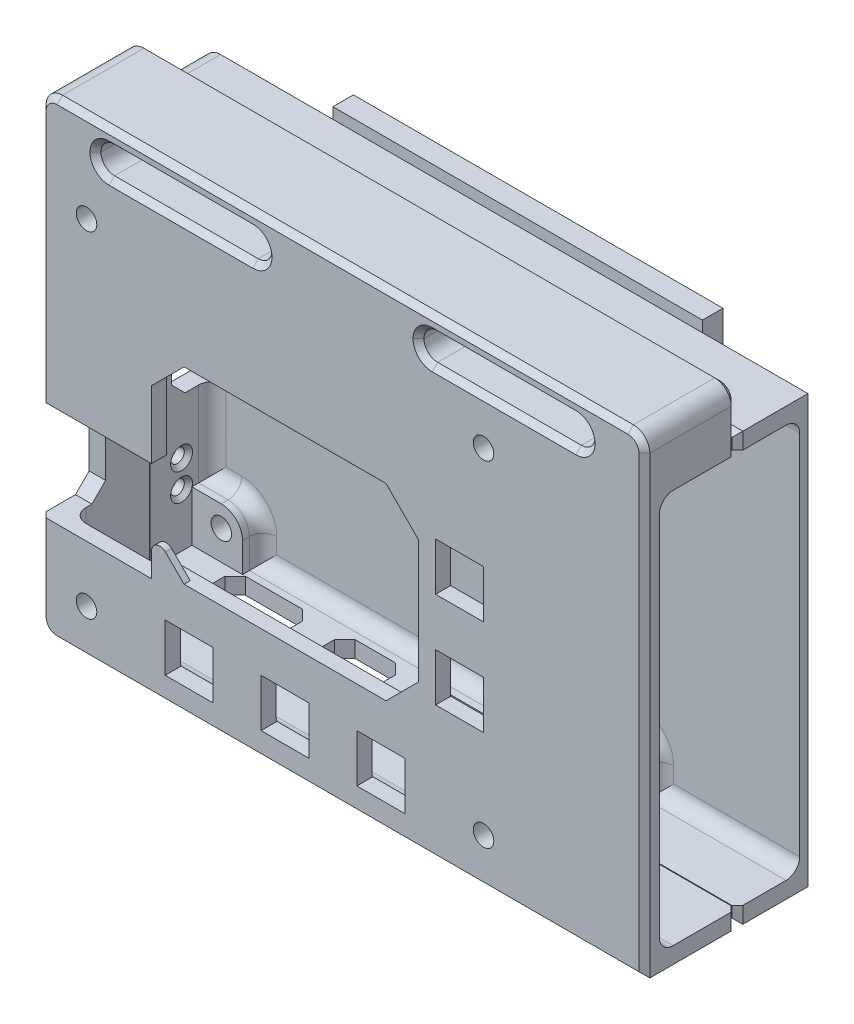
SolidWorks part; units mm, degrees
other "Bottom"
other "Top"
other "Charger-Plate" parameters "D1"=2, "D2"=2.4, "D3"=2.4, "D4"=4
ref_plane "Front Plane" through (0, 0, 0) normal (0, 0, 1) x (1, 0, 0)
ref_plane "Top Plane" through (0, 0, 0) normal (0, 1, 0) x (1, 0, 0)
ref_plane "Right Plane" through (0, 0, 0) normal (1, 0, 0) x (0, 0, -1)
ref_plane "Plane1" through (0, 0, 18.2875) normal (0, 0, 1) x (1, 0, 0)
sketch "Sketch1" plane through (0, 0, 16.2) normal (0, 0, 1) x (1, 0, 0)
  line L0 (13, 36.15) -> (17.75, 40.9)
  line L1 (17.75, 40.9) -> (47.25, 40.9)
  line L2 (47.25, 40.9) -> (52, 36.15)
  line L3 (52, 36.15) -> (52, 18.15)
  line L4 (52, 18.15) -> (47.25, 13.4)
  line L5 (47.25, 13.4) -> (17.75, 13.4)
  line L6 (17.75, 13.4) -> (13, 18.15)
  line L7 (13, 18.15) -> (13, 36.15)
  line L8 (13, 27.15) -> (52, 27.15) construction
  line L9 (32.5, 13.4) -> (32.5, 40.9) construction
  point P12 (32.5, 27.15)
sketch "Sketch2" plane through (0, 0, 18.2875) normal (0, 0, 1) x (1, 0, 0)
  line L0 (85, 56.8) -> (85, 59.2)
  line L1 (85, 59.2) -> (-3.2, 59.2)
  line L2 (-3.2, 59.2) -> (-3.2, -3.2)
  line L3 (-3.2, -3.2) -> (85, -3.2)
  line L4 (85, -3.2) -> (85, -0.8)
  line L5 (85, -0.8) -> (-0.8, -0.8)
  line L6 (-0.8, -0.8) -> (-0.8, 56.8)
  line L7 (-0.8, 56.8) -> (85, 56.8)
  line L8 (-0.8, 28) -> (-3.2, 28) construction
  line L9 (-0.8, 28) -> (0, 28) construction
  line L10 (0, 53) -> (0, 3) construction
  line L11 (42.1, 56.8) -> (42.1, 56) construction
  line L12 (82, 56) -> (3, 56) construction
  line L13 (42.1, -0.8) -> (42.1, 0) construction
  line L14 (3, 0) -> (82, 0) construction
  line L15 (85, 3) -> (85, 53) construction
  dimension "D1" = 0.8
  dimension "D2" = 2.4
extrude "Boss-Extrude1" add sketch "Sketch2" against normal offset from surface (13.1275 mm away) 2
sketch "Sketch3" plane through (0, 0, 18.2875) normal (0, 0, 1) x (1, 0, 0)
  line L1 (85, -3.2) -> (-3.2, -3.2)
  line L2 (85, -3.2) -> (85, 59.2)
  line L3 (85, 59.2) -> (-3.2, 59.2)
  line L4 (-3.2, -3.2) -> (-3.2, 59.2)
  line L5 (40.9, 59.2) -> (40.9, -3.2) construction
  line L6 (85, 28) -> (-3.2, 28) construction
  point P0 (40.9, 28)
extrude "Boss-Extrude2" add sketch "Sketch3" against normal blind 1.8 and the other way blind 0.4
extrude "Cut-Extrude1" cut sketch "Sketch1" along normal through all
sketch "Sketch4" plane through (0, 0, 16.4875) normal (0, 0, -1) x (-1, 0, 0)
  line L0 (-32.5, 40.9) -> (-32.5, 13.4) construction
  line L1 (-13, 40.9) -> (-52, 40.9)
  line L2 (-13, 40.9) -> (-13, 13.4)
  line L3 (-13, 13.4) -> (-52, 13.4)
  line L4 (-52, 40.9) -> (-52, 13.4)
  line L5 (-32.5, 13.4) -> (-32.5, 40.9) construction
  line L6 (-13, 27.15) -> (-52, 27.15) construction
  line L10 (-13, 13.4) -> (-52, 13.4) construction
  line L11 (-13, 40.9) -> (-52, 40.9) construction
  line L12 (-52, 36.15) -> (-52, 18.15) construction
  point P0 (-32.5, 27.15)
extrude "Cut-Extrude2" cut sketch "Sketch4" against normal offset from surface (1.3 mm away) 0.9 up to face at (40.9, 28, 18.6875)
sketch "Sketch15" plane through (0, 0, 16.4875) normal (0, 0, -1) x (-1, 0, 0)
  line L0 (-52, 10.1) -> (-52, 47.9) construction
  line L1 (-13, 49.9) -> (-52, 49.9)
  line L2 (-13, 49.9) -> (-13, 45.9)
  line L3 (-13, 45.9) -> (-52, 45.9)
  line L4 (-52, 49.9) -> (-52, 45.9)
  line L5 (-32.5, 45.9) -> (-32.5, 49.9) construction
  line L6 (-13, 47.9) -> (-52, 47.9) construction
  line L8 (-41, 12.1) -> (-52, 12.1)
  line L9 (-41, 12.1) -> (-41, 8.1)
  line L10 (-41, 8.1) -> (-52, 8.1)
  line L11 (-52, 12.1) -> (-52, 8.1)
  line L12 (-46.5, 8.1) -> (-46.5, 12.1) construction
  line L13 (-41, 10.1) -> (-52, 10.1) construction
  line L14 (-24, 12.1) -> (-13, 12.1)
  line L15 (-24, 12.1) -> (-24, 8.1)
  line L16 (-24, 8.1) -> (-13, 8.1)
  line L17 (-13, 12.1) -> (-13, 8.1)
  line L18 (-18.5, 8.1) -> (-18.5, 12.1) construction
  line L19 (-24, 10.1) -> (-13, 10.1) construction
  point P0 (-32.5, 47.9)
  point P5 (-18.5, 10.1)
  point P8 (-46.5, 10.1)
  dimension "D1" = 4
  dimension "D2" = 11
extrude "Cut-Extrude8" cut sketch "Sketch15" against normal blind 1
sketch "Sketch5" plane through (0, 0, 16.4875) normal (0, 0, -1) x (-1, 0, 0)
  line L0 (-52.8159, -0.8) -> (-64.6, -0.8)
  line L1 (-64.6, -0.8) -> (-64.6, 3.5)
  line L2 (-59.308, 5.692) -> (-52.8159, -0.8)
  line L3 (-85, -0.8) -> (0.8, -0.8) construction
  line L4 (-6.6, 3.5) -> (-6.6, -0.8)
  line L5 (-6.6, -0.8) -> (0.8, -0.8)
  line L7 (-3.5, 6.6) -> (0.8, 6.6)
  line L8 (0.8, 6.6) -> (0.8, -0.8)
  line L9 (-980.0493, 28) -> (49019.9507, 28) construction
  line L10 (0.8, 49.4) -> (0.8, 56.8)
  line L11 (-3.5, 49.4) -> (0.8, 49.4)
  line L12 (-6.6, 56.8) -> (0.8, 56.8)
  line L13 (-6.6, 52.5) -> (-6.6, 56.8)
  line L14 (-59.308, 50.308) -> (-52.8159, 56.8)
  line L15 (-64.6, 56.8) -> (-64.6, 52.5)
  line L16 (-52.8159, 56.8) -> (-64.6, 56.8)
  arc A0 (-64.6, 3.5) -> (-59.308, 5.692) centre (-61.5, 3.5) cw
  circle A1 centre (-61.5, 3.5) radius 1.5
  circle A2 centre (-61.5, 3.5) radius 1.5 construction
  arc A3 (-6.6, 3.5) -> (-3.5, 6.6) centre (-3.5, 3.5) cw
  circle A4 centre (-3.5, 3.5) radius 1.5
  circle A5 centre (-3.5, 3.5) radius 1.5 construction
  circle A6 centre (-3.5, 52.5) radius 1.5
  arc A7 (-6.6, 52.5) -> (-3.5, 49.4) centre (-3.5, 52.5) ccw
  circle A8 centre (-61.5, 52.5) radius 1.5
  arc A9 (-64.6, 52.5) -> (-59.308, 50.308) centre (-61.5, 52.5) ccw
  point P6 (-61.5, 6.6)
  point P7 (-61.5, 5)
  point P39 (-61.5, 51)
  point P40 (-61.5, 49.4)
  dimension "D1" = 3
  dimension "D2" = 1.6
  dimension "D3" = 45
extrude "Boss-Extrude3" add sketch "Sketch5" along normal up to surface (2.8875 mm away)
sketch "Sketch17" plane through (0, 0, 16.4875) normal (0, 0, -1) x (-1, 0, 0)
  circle A0 centre (-3.5, 3.5) radius 1.5 construction
  circle A1 centre (-3.5, 52.5) radius 1.5 construction
  circle A2 centre (-61.5, 52.5) radius 1.5 construction
  circle A3 centre (-61.5, 3.5) radius 1.5 construction
  circle A4 centre (-3.5, 3.5) radius 1.5
  circle A5 centre (-3.5, 52.5) radius 1.5
  circle A6 centre (-61.5, 52.5) radius 1.5
  circle A7 centre (-61.5, 3.5) radius 1.5
extrude "Cut-Extrude9" cut sketch "Sketch17" against normal through all
sketch "Sketch6" plane through (0, 0, 18.6875) normal (0, 0, 1) x (1, 0, 0)
  line L0 (54.5, 16.5) -> (61.5, 16.5)
  line L1 (61.5, 16.5) -> (61.5, 23.5)
  line L2 (61.5, 23.5) -> (54.5, 23.5)
  line L3 (54.5, 23.5) -> (54.5, 16.5)
  line L4 (55, 17) -> (61, 17)
  line L5 (55, 23) -> (55, 17)
  line L6 (61, 23) -> (55, 23)
  line L7 (61, 17) -> (61, 23)
  line L8 (55, 17) -> (61, 17) construction
  line L9 (55, 23) -> (55, 17) construction
  line L10 (61, 23) -> (55, 23) construction
  line L11 (61, 17) -> (61, 23) construction
  line L12 (55, 31) -> (61, 31)
  line L13 (55, 37) -> (55, 31)
  line L14 (61, 37) -> (55, 37)
  line L15 (61, 31) -> (61, 37)
  line L16 (55, 31) -> (61, 31) construction
  line L17 (55, 37) -> (55, 31) construction
  line L18 (61, 37) -> (55, 37) construction
  line L19 (61, 31) -> (61, 37) construction
  line L20 (15.5, 1) -> (21.5, 1)
  line L21 (15.5, 7) -> (15.5, 1)
  line L22 (21.5, 7) -> (15.5, 7)
  line L23 (21.5, 1) -> (21.5, 7)
  line L24 (15.5, 1) -> (21.5, 1) construction
  line L25 (15.5, 7) -> (15.5, 1) construction
  line L26 (21.5, 7) -> (15.5, 7) construction
  line L27 (21.5, 1) -> (21.5, 7) construction
  line L28 (43.5, 1) -> (49.5, 1)
  line L29 (43.5, 7) -> (43.5, 1)
  line L30 (49.5, 7) -> (43.5, 7)
  line L31 (49.5, 1) -> (49.5, 7)
  line L32 (43.5, 1) -> (49.5, 1) construction
  line L33 (43.5, 7) -> (43.5, 1) construction
  line L34 (49.5, 7) -> (43.5, 7) construction
  line L35 (49.5, 1) -> (49.5, 7) construction
  line L36 (29.5, 1) -> (35.5, 1)
  line L37 (29.5, 7) -> (29.5, 1)
  line L38 (35.5, 7) -> (29.5, 7)
  line L39 (35.5, 1) -> (35.5, 7)
  line L40 (29.5, 1) -> (35.5, 1) construction
  line L41 (29.5, 7) -> (29.5, 1) construction
  line L42 (35.5, 7) -> (29.5, 7) construction
  line L43 (35.5, 1) -> (35.5, 7) construction
  line L44 (54.5, 30.5) -> (61.5, 30.5)
  line L45 (61.5, 30.5) -> (61.5, 37.5)
  line L46 (61.5, 37.5) -> (54.5, 37.5)
  line L47 (54.5, 37.5) -> (54.5, 30.5)
  line L48 (15, 0.5) -> (22, 0.5)
  line L49 (22, 0.5) -> (22, 7.5)
  line L50 (22, 7.5) -> (15, 7.5)
  line L51 (15, 7.5) -> (15, 0.5)
  line L52 (43, 0.5) -> (50, 0.5)
  line L53 (50, 0.5) -> (50, 7.5)
  line L54 (50, 7.5) -> (43, 7.5)
  line L55 (43, 7.5) -> (43, 0.5)
  line L56 (29, 0.5) -> (36, 0.5)
  line L57 (36, 0.5) -> (36, 7.5)
  line L58 (36, 7.5) -> (29, 7.5)
  line L59 (29, 7.5) -> (29, 0.5)
  dimension "D1" = 0
  dimension "D2" = 0
  dimension "D3" = 0
  dimension "D4" = 0
  dimension "D5" = 0
  dimension "D6" = 0.5
extrude "Cut-Extrude3" cut sketch "Sketch6" against normal through all
sketch "Sketch7" plane through (0, 0, 18.6875) normal (0, 0, 1) x (1, 0, 0)
  line L0 (13, 18.15) -> (13, 36.15) construction
  line L1 (-3.2, 11.715) -> (13, 11.715)
  line L2 (-3.2, 11.715) -> (-3.2, 26.285)
  line L3 (-3.2, 26.285) -> (13, 26.285)
  line L4 (13, 11.715) -> (13, 26.285)
  line L5 (4.9, 26.285) -> (4.9, 11.715) construction
  line L6 (-3.2, 19) -> (13, 19) construction
  line L7 (-3.2, 59.2) -> (-3.2, -3.2) construction
  line L8 (-0.67, 19) -> (11.9, 19) construction
  line L9 (-0.67, 25.285) -> (11.9, 25.285) construction
  point P0 (4.9, 19)
  dimension "D1" = 1
extrude "Cut-Extrude4" cut sketch "Sketch7" against normal offset from surface (7.0875 mm away) 2 up to face at (3.5, 5, 13.6) offset beyond the face yes
sketch "Sketch8" plane through (0, 0, 5.16) normal (0, 0, -1) x (-1, 0, 0)
  line L8 (-85, 59.2) -> (-85, 56.8)
  line L9 (3.2, 59.2) -> (-85, 59.2)
  line L10 (3.2, -3.2) -> (3.2, 59.2)
  line L11 (-85, -3.2) -> (3.2, -3.2)
  line L12 (-85, -0.8) -> (-85, -3.2)
  line L13 (0.8, -0.8) -> (-85, -0.8)
  line L14 (0.8, 56.8) -> (0.8, -0.8)
  line L15 (-85, 56.8) -> (0.8, 56.8)
  line L16 (-85, 59.2) -> (-85, 56.8)
  line L17 (3.2, 59.2) -> (-85, 59.2)
  line L18 (3.2, -3.2) -> (3.2, 59.2)
  line L19 (-85, -3.2) -> (3.2, -3.2)
  line L20 (-85, -0.8) -> (-85, -3.2)
  line L21 (0.8, -0.8) -> (-85, -0.8)
  line L22 (0.8, 56.8) -> (0.8, -0.8)
  line L23 (-85, 56.8) -> (0.8, 56.8)
  dimension "D1" = 0
extrude "Boss-Extrude4" add sketch "Sketch8" along normal offset from surface (9.16 mm away) 3 separate body offset beyond the face yes
sketch "Sketch9" plane through (0, 0, -4) normal (0, 0, -1) x (-1, 0, 0)
  line L4 (-85, -3.2) -> (3.2, -3.2)
  line L5 (-85, 59.2) -> (-85, -3.2)
  line L6 (3.2, 59.2) -> (-85, 59.2)
  line L7 (3.2, -3.2) -> (3.2, 59.2)
  line L8 (-85, -3.2) -> (3.2, -3.2)
  line L9 (-85, 59.2) -> (-85, -3.2)
  line L10 (3.2, 59.2) -> (-85, 59.2)
  line L11 (3.2, -3.2) -> (3.2, 59.2)
  circle A0 centre (-3.5, 52.5) radius 1.5 construction
  circle A1 centre (-61.5, 52.5) radius 1.5 construction
  circle A2 centre (-61.5, 3.5) radius 1.5 construction
  circle A3 centre (-3.5, 3.5) radius 1.5 construction
  circle A4 centre (-3.5, 52.5) radius 1.5
  circle A5 centre (-61.5, 52.5) radius 1.5
  circle A6 centre (-61.5, 3.5) radius 1.5
  circle A7 centre (-3.5, 3.5) radius 1.5
  dimension "D1" = 0
extrude "Boss-Extrude5" add sketch "Sketch9" along normal blind 2
sketch "Sketch10" plane through (0, 0, -4) normal (0, 0, 1) x (1, 0, 0)
  line L3 (52.8159, -0.8) -> (64.6, -0.8)
  line L4 (64.6, -0.8) -> (64.6, 3.5)
  line L5 (59.308, 5.692) -> (52.8159, -0.8)
  line L6 (52.8159, -0.8) -> (64.6, -0.8)
  line L7 (64.6, -0.8) -> (64.6, 3.5)
  line L8 (59.308, 5.692) -> (52.8159, -0.8)
  line L9 (52.8159, 56.8) -> (59.308, 50.308)
  line L10 (-0.8, -0.8) -> (6.6, -0.8)
  line L11 (-0.8, 6.6) -> (-0.8, -0.8)
  line L12 (3.5, 6.6) -> (-0.8, 6.6)
  line L13 (6.6, -0.8) -> (6.6, 3.5)
  line L14 (-0.8, -0.8) -> (6.6, -0.8)
  line L15 (-0.8, 6.6) -> (-0.8, -0.8)
  line L16 (3.5, 6.6) -> (-0.8, 6.6)
  line L17 (6.6, -0.8) -> (6.6, 3.5)
  line L18 (64.6, 56.8) -> (52.8159, 56.8)
  line L19 (64.6, 52.5) -> (64.6, 56.8)
  line L20 (52.8159, 56.8) -> (59.308, 50.308)
  line L21 (64.6, 56.8) -> (52.8159, 56.8)
  line L22 (64.6, 52.5) -> (64.6, 56.8)
  line L24 (-0.8, 56.8) -> (-0.8, 49.4)
  line L25 (6.6, 56.8) -> (-0.8, 56.8)
  line L26 (6.6, 52.5) -> (6.6, 56.8)
  line L27 (-0.8, 49.4) -> (3.5, 49.4)
  line L28 (-0.8, 56.8) -> (-0.8, 49.4)
  line L29 (6.6, 56.8) -> (-0.8, 56.8)
  line L30 (6.6, 52.5) -> (6.6, 56.8)
  line L31 (-0.8, 49.4) -> (3.5, 49.4)
  circle A1 centre (3.5, 3.5) radius 1.5
  circle A2 centre (3.5, 3.5) radius 1.5
  circle A3 centre (61.5, 3.5) radius 1.5
  circle A4 centre (61.5, 3.5) radius 1.5
  arc A5 (64.6, 3.5) -> (59.308, 5.692) centre (61.5, 3.5) ccw
  arc A6 (64.6, 3.5) -> (59.308, 5.692) centre (61.5, 3.5) ccw
  circle A7 centre (61.5, 52.5) radius 1.5
  circle A8 centre (61.5, 52.5) radius 1.5
  circle A9 centre (3.5, 52.5) radius 1.5
  circle A10 centre (3.5, 52.5) radius 1.5
  arc A11 (6.6, 3.5) -> (3.5, 6.6) centre (3.5, 3.5) ccw
  arc A12 (6.6, 3.5) -> (3.5, 6.6) centre (3.5, 3.5) ccw
  arc A13 (59.308, 50.308) -> (64.6, 52.5) centre (61.5, 52.5) ccw
  arc A14 (59.308, 50.308) -> (64.6, 52.5) centre (61.5, 52.5) ccw
  arc A15 (3.5, 49.4) -> (6.6, 52.5) centre (3.5, 52.5) ccw
  arc A16 (3.5, 49.4) -> (6.6, 52.5) centre (3.5, 52.5) ccw
  dimension "D1" = 0
  dimension "D2" = 0
  dimension "D3" = 0
  dimension "D4" = 0
  dimension "D5" = 0
  dimension "D6" = 0
  dimension "D7" = 0
  dimension "D8" = 0
extrude "Boss-Extrude6" add sketch "Sketch10" along normal up to surface (3 mm away)
sketch "Sketch11" plane through (0, 0, -6) normal (0, 0, -1) x (-1, 0, 0)
  line L0 (3.2, 59.2) -> (3.2, -3.2) construction
  line L1 (-5.647, 37) -> (3.2, 37)
  line L2 (-5.647, 37) -> (-5.647, 19)
  line L3 (-5.647, 19) -> (3.2, 19)
  line L4 (3.2, 37) -> (3.2, 19)
  line L5 (-1.2235, 19) -> (-1.2235, 37) construction
  line L6 (-5.647, 28) -> (3.2, 28) construction
  line L7 (-85, 28) -> (3.2, 28) construction
  line L8 (-3.647, 22.4017) -> (-3.647, 30.9017) construction
  point P0 (-1.2235, 28)
  dimension "D1" = 18
  dimension "D2" = 2
extrude "Cut-Extrude5" cut sketch "Sketch11" against normal offset from surface (8 mm away) 2 offset beyond the face yes
sketch "Sketch12" plane through (0, -3.2, 0) normal (0, -1, 0) x (1, 0, 0)
  line L0 (50, 2.9) -> (50, 5.16)
  line L1 (85, 5.16) -> (-3.2, 5.16) construction
  line L2 (50, 5.16) -> (50.6996, 5.16)
  line L3 (58, 2.9) -> (58, 5.16)
  line L4 (58, 5.16) -> (57.3004, 5.16)
  line L5 (3, -1) -> (82, -1) construction
  line L6 (21.55, -1) -> (30.47, -1)
  line L7 (21.55, -1) -> (21.55, 5.16)
  line L8 (21.55, 5.16) -> (30.47, 5.16)
  line L9 (30.47, -1) -> (30.47, 5.16)
  line L10 (26.01, 5.16) -> (26.01, -1) construction
  line L11 (21.55, 2.08) -> (30.47, 2.08) construction
  line L12 (22.75, 2.4) -> (22.75, 1.0798) construction
  line L13 (9.95, 3.16) -> (12.45, 3.16) construction
  line L14 (35.05, -1) -> (43.97, -1)
  line L15 (35.05, -1) -> (35.05, 5.16)
  line L16 (35.05, 5.16) -> (43.97, 5.16)
  line L17 (43.97, -1) -> (43.97, 5.16)
  line L18 (39.51, 5.16) -> (39.51, -1) construction
  line L19 (35.05, 2.08) -> (43.97, 2.08) construction
  line L20 (5.53, -1) -> (16.87, -1)
  line L21 (5.53, -1) -> (5.53, 5.16)
  line L22 (5.53, 5.16) -> (16.87, 5.16)
  line L23 (16.87, -1) -> (16.87, 5.16)
  line L24 (11.2, 5.16) -> (11.2, -1) construction
  line L25 (5.53, 2.08) -> (16.87, 2.08) construction
  line L26 (15.67, -0.65) -> (15.67, 1.38) construction
  circle A0 centre (54, 2.9) radius 4 construction
  arc A1 (51, 2.9) -> (57, 2.9) centre (54, 2.9) ccw construction
  arc A2 (50, 2.9) -> (58, 2.9) centre (54, 2.9) ccw
  arc A3 (50.6996, 5.16) -> (57.3004, 5.16) centre (54, 2.9) cw
  point P5 (58, 2.9)
  point P18 (26.01, 2.08)
  point P26 (39.51, 2.08)
  point P30 (11.2, 2.08)
  point P36 (11.2, 3.16)
  dimension "D1" = 1
  dimension "D2" = 1.2
  dimension "D3" = 1.2
extrude "Cut-Extrude6" cut sketch "Sketch12" against normal up to surface (2.4 mm away) up to face at (41.6432, -0.8, -0.968)
chamfer "Chamfer1" distance 1.5 angle 45 6 edges at (5.53, -2, -1) (16.87, -2, -1) (30.47, -2, -1) (21.55, -2, -1) (35.05, -2, -1) (43.97, -2, -1)
fillet "Fillet1" radius 2 18 edges at (1.35, 49.4, -4) (6.6, 54.65, -4) (56.062, 53.554, -4) (64.6, 54.65, -4) (64.6, 1.35, -4) (56.062, 2.446, -4) (6.6, 1.35, -4) (1.35, 6.6, -4) (74.8, -0.8, -4) (-0.8, 12.8, -4) (29.708, -0.8, -4) (74.8, 56.8, -4) (29.708, 56.8, -4) (-0.8, 43.2, -4) (5.692, 50.308, -4) (62.6863, 49.636, -4) (62.6863, 6.364, -4) (5.692, 5.692, -4)
fillet "Fillet2" radius 2 18 edges at (64.6, 54.65, 16.4875) (56.062, 53.554, 16.4875) (6.6, 54.65, 16.4875) (1.35, 49.4, 16.4875) (1.35, 6.6, 16.4875) (6.6, 1.35, 16.4875) (56.062, 2.446, 16.4875) (64.6, 1.35, 16.4875) (29.708, 56.8, 16.4875) (74.8, 56.8, 16.4875) (62.6863, 49.636, 16.4875) (5.692, 50.308, 16.4875) (-0.8, 37.8425, 16.4875) (-0.8, 9.1575, 16.4875) (5.692, 5.692, 16.4875) (74.8, -0.8, 16.4875) (29.708, -0.8, 16.4875) (62.6863, 6.364, 16.4875)
sketch "Sketch14" plane through (0, 59.2, 0) normal (0, 1, 0) x (1, 0, 0)
  line L0 (-3.2, -5.16) -> (85, -5.16) construction
  line L1 (85, -5.11) -> (-3.2, -5.11)
  line L2 (85, -5.11) -> (85, -5.21)
  line L3 (85, -5.21) -> (-3.2, -5.21)
  line L4 (-3.2, -5.11) -> (-3.2, -5.21)
  line L5 (40.9, -5.21) -> (40.9, -5.11) construction
  line L6 (85, -5.16) -> (-3.2, -5.16) construction
  line L7 (-3.2, -5.16) -> (-3.2, -18.6875) construction
  point P0 (40.9, -5.16)
  dimension "D1" = 0.1
extrude "Cut-Extrude7" cut sketch "Sketch14" against normal through all
sketch "Sketch16" plane through (0, 0, 18.6875) normal (0, 0, 1) x (1, 0, 0)
  line L0 (4.8, 59.2) -> (-3.2, 59.2)
  line L1 (4.8, 59.2) -> (29.8, 59.2) construction
  line L2 (4.8, 59.2) -> (4.8, 63.2)
  line L3 (4.8, 63.2) -> (29.8, 63.2)
  line L4 (29.8, 59.2) -> (29.8, 63.2)
  line L5 (17.3, 63.2) -> (17.3, 59.2) construction
  line L6 (4.8, 61.2) -> (29.8, 61.2) construction
  line L7 (52, 59.2) -> (77, 59.2) construction
  line L8 (52, 59.2) -> (52, 63.2)
  line L9 (52, 63.2) -> (77, 63.2)
  line L10 (77, 59.2) -> (77, 63.2)
  line L11 (64.5, 63.2) -> (64.5, 59.2) construction
  line L12 (52, 61.2) -> (77, 61.2) construction
  line L13 (-3.2, 59.2) -> (-3.2, 65.6)
  line L14 (-3.2, 65.6) -> (85, 65.6)
  line L15 (85, 65.6) -> (85, 59.2)
  line L16 (85, 59.2) -> (77, 59.2)
  line L17 (17.3, 63.2) -> (17.3, 65.6) construction
  line L19 (52, 59.2) -> (29.8, 59.2)
  line L20 (-0.8, 28) -> (-3.2, 28) construction
  point P0 (17.3, 61.2)
  point P4 (64.5, 61.2)
  dimension "D1" = 25
  dimension "D2" = 4
  dimension "D3" = 8
  dimension "D4" = 72.2
extrude "Boss-Extrude7" add sketch "Sketch16" against normal up to surface (13.4775 mm away) up to face at (32.9336, 28, 5.21)
sketch "Sketch21" plane through (-3.2, 0, 0) normal (-1, 0, 0) x (0, 0, 1)
  line L0 (0, 53) -> (0, 3) construction
  circle A0 centre (0.5, 11) radius 1
  circle A1 centre (0.5, 7) radius 1
  point P4 (0, 0)
  dimension "D1" = 2
  dimension "D2" = 7
  dimension "D3" = 11
  dimension "D4" = 0.5
extrude "Cut-Extrude11" cut sketch "Sketch21" against normal blind 4
chamfer "Chamfer10" distance 0.6 angle 45 4 edges at (-0.8, 7, 1.5) (-3.2, 6, 0.5) (-0.8, 11, 1.5) (-3.2, 10, 0.5)
chamfer "Chamfer7" distance 0.8 angle 45 1 edges at (40.9, 65.6, 5.21)
fillet "Fillet3" radius 2 8 edges at (77, 59.2, 11.9487) (77, 63.2, 11.9487) (52, 63.2, 11.9487) (52, 59.2, 11.9487) (4.8, 59.2, 11.9487) (29.8, 59.2, 11.9487) (29.8, 63.2, 11.9487) (4.8, 63.2, 11.9487)
fillet "Fillet4" radius 2.4 3 edges at (-3.2, -3.2, 11.9487) (-3.2, 65.6, 12.3487) (85, 65.6, 12.3487)
fillet "Fillet5" radius 2.4 2 edges at (-3.2, -3.2, -0.445) (-3.2, 59.2, -0.445)
chamfer "Chamfer2" distance 0.8 angle 45 20 edges at (42.1, -3.2, 18.6875) (-2.4971, -2.4971, 18.6875) (-3.2, 5.4575, 18.6875) (85, 30, 18.6875) (-3.2, 44.7425, 18.6875) (84.2971, 64.8971, 18.6875) (-2.4971, 64.8971, 18.6875) (40.9, 65.6, 18.6875) (64.5, 63.2, 18.6875) (76.4142, 62.6142, 18.6875) (52.5858, 62.6142, 18.6875) (76.4142, 59.7858, 18.6875) (52.5858, 59.7858, 18.6875) (64.5, 59.2, 18.6875) (17.3, 63.2, 18.6875) (29.2142, 62.6142, 18.6875) (5.3858, 62.6142, 18.6875) (29.2142, 59.7858, 18.6875) (5.3858, 59.7858, 18.6875) (17.3, 59.2, 18.6875)
chamfer "Chamfer3" distance 0.8 angle 45 7 edges at (-3.2, 46.9, -6) (-3.2, 9.1, -6) (-2.4971, 58.4971, -6) (-2.4971, -2.4971, -6) (42.1, 59.2, -6) (42.1, -3.2, -6) (85, 28, -6)
fillet "Fillet6" radius 1.2 1 edges at (13, 18.15, 18.2375)
chamfer "Chamfer4-Screws-Countersink" [suppressed] distance 2 angle 45
chamfer "Chamfer5" distance 2 angle 45 2 edges at (-2, 19, 2) (-2, 37, 2)
chamfer "Chamfer6" distance 2 angle 45 2 edges at (-2, 26.285, 11.6) (-2, 11.715, 11.6)
sketch "Sketch18" plane through (0, 0, -6) normal (0, 0, -1) x (-1, 0, 0)
  line L0 (3.2, 59.2) -> (3.2, -3.2) construction
  line L1 (-121.8, 63) -> (3.2, 63) construction
  line L2 (-121.8, 63) -> (-121.8, -7) construction
  line L3 (-121.8, -7) -> (3.2, -7) construction
  line L4 (3.2, 63) -> (3.2, -7) construction
  line L5 (-59.3, -7) -> (-59.3, 63) construction
  line L6 (-121.8, 28) -> (3.2, 28) construction
  line L8 (-68.8, 60) -> (-14.8, 60)
  line L9 (-68.8, 60) -> (-68.8, -4)
  line L10 (-68.8, -4) -> (-14.8, -4)
  line L11 (-14.8, 60) -> (-14.8, -4)
  line L12 (-41.8, -4) -> (-41.8, 60) construction
  line L13 (-68.8, 28) -> (-14.8, 28) construction
  point P0 (-59.3, 28)
  point P7 (-41.8, 28)
  dimension "D1" = 70
  dimension "D2" = 125
  dimension "D3" = 18
  dimension "D4" = 64
  dimension "D5" = 53
extrude "Boss-Extrude8" add sketch "Sketch18" along normal blind 3 separate body
sketch "Sketch20" plane through (0, 0, -9) normal (0, 0, -1) x (-1, 0, 0)
  line L0 (-41.8, 53.5) -> (-41.8, 2.5) construction
  line L1 (-121.8, 28) -> (3.2, 28) construction
  circle A0 centre (-41.8, 53.5) radius 1.3
  circle A1 centre (-41.8, 2.5) radius 1.3
  circle A2 centre (-61.5, 52.5) radius 4
  circle A3 centre (-61.5, 3.5) radius 4
  circle A4 centre (-61.5, 52.5) radius 1.5 construction
  circle A5 centre (-61.5, 3.5) radius 1.5 construction
  point P2 (-41.8, 28)
  dimension "D1" = 2.6
  dimension "D3" = 8
  dimension "D2" = 51
extrude "Cut-Extrude10" cut sketch "Sketch20" against normal through all
chamfer "Chamfer8" distance 0.8 angle 45 8 edges at (84.842, 64.0564, 5.21) (85, 60, 5.21) (-3.042, 64.0564, 5.21) (-3.2, 31.2, 5.21) (-2.4971, -2.4971, 5.21) (24.9672, -3.2, 5.21) (85, -2, 5.21) (71.1328, -3.2, 5.21)
chamfer "Chamfer9" distance 0.8 angle 45 11 edges at (85, 58, 5.11) (42.1, 59.2, 5.11) (-2.4971, 58.4971, 5.11) (-3.2, 28, 5.11) (-2.4971, -2.4971, 5.11) (2.365, -3.2, 5.11) (19.21, -3.2, 5.11) (32.76, -3.2, 5.11) (46.985, -3.2, 5.11) (71.5, -3.2, 5.11) (85, -2, 5.11)
sketch "Sketch19" plane through (0, 0, -9) normal (0, 0, -1) x (-1, 0, 0)
  line L1 (-68.8, -6) -> (-14.8, -6)
  line L2 (-68.8, -6) -> (-68.8, -4)
  line L3 (-68.8, -4) -> (-14.8, -4)
  line L4 (-14.8, -6) -> (-14.8, -4)
  line L5 (-41.8, -4) -> (-41.8, -6) construction
  line L6 (-68.8, -5) -> (-14.8, -5) construction
  line L7 (-14.8, -3.6) -> (-68.8, -3.6) construction
  line L8 (3.2, -3.2) -> (-85, -3.2) construction
  line L10 (-14.8, 62) -> (-68.8, 62)
  line L11 (-14.8, 62) -> (-14.8, 60)
  line L12 (-14.8, 60) -> (-68.8, 60)
  line L13 (-68.8, 62) -> (-68.8, 60)
  line L14 (-41.8, 60) -> (-41.8, 62) construction
  line L15 (-14.8, 61) -> (-68.8, 61) construction
  point P0 (-41.8, -5)
  point P6 (-41.8, 61)
  dimension "D1" = 0.4
  dimension "D2" = 2.4
extrude "Boss-Extrude9" [suppressed] add sketch "Sketch19" against normal up to surface (13.76 mm away)
fillet "Fillet7" radius 3 2 edges at (5.647, 19, -5) (5.647, 37, -5)
equation "\"D1@Fillet2\"=\"D1@Fillet1\""
equation "\"D1@Fillet3\"=\"D2@Sketch16\"/2"
equation "\"D1@Fillet4\"=\"D2@Sketch2\""
equation "\"D1@Fillet5\"=\"D1@Fillet4\""
equation "\"D1@Chamfer3\"=\"D1@Chamfer2\""
equation "\"D1@Chamfer9\"=\"D1@Chamfer8\""
